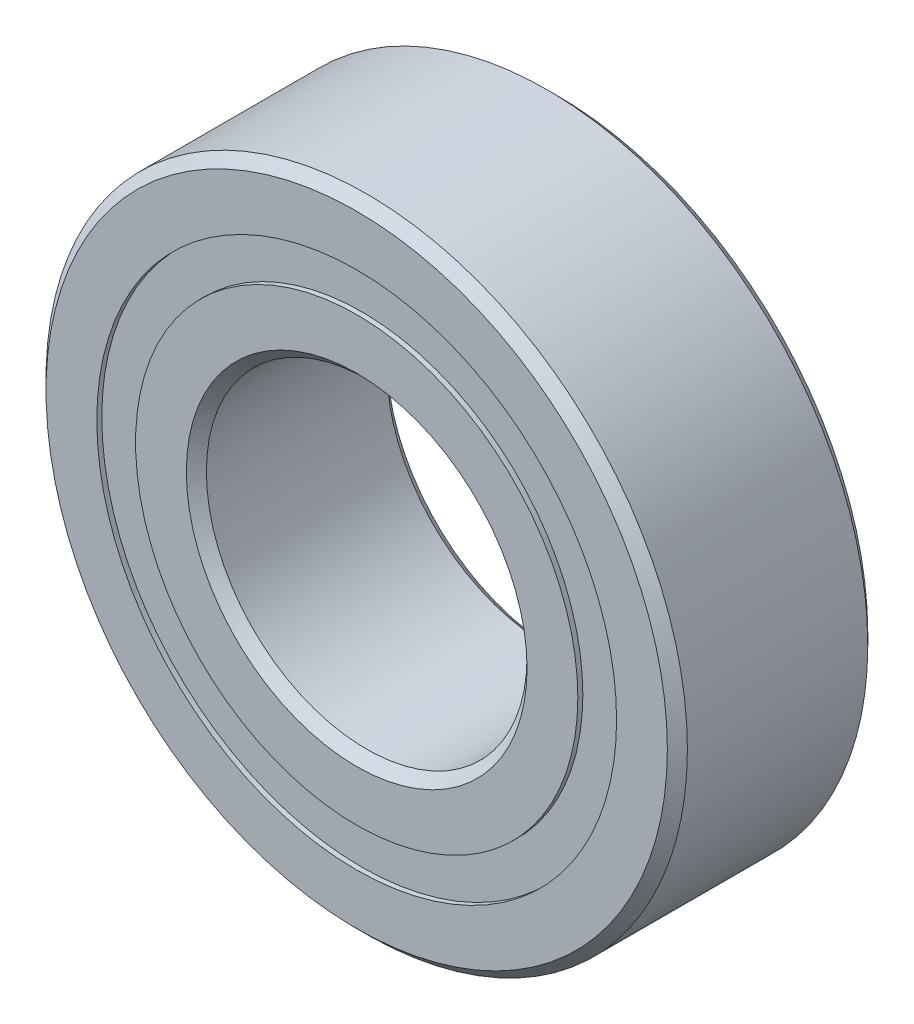
SolidWorks part; units mm, degrees
ref_plane "Front Plane" through (0, 0, 0) normal (0, 0, 1) x (1, 0, 0)
ref_plane "Top Plane" through (0, 0, 0) normal (0, 1, 0) x (1, 0, 0)
ref_plane "Right Plane" through (0, 0, 0) normal (1, 0, 0) x (0, 0, -1)
sketch "Sketch1" plane through (0, 0, 0) normal (1, 0, 0) x (0, 0, -1)
  line L0 (-2.5, 0) -> (2.5, 0) construction
  line L1 (0, 8) -> (0, -8) construction
  line L2 (2.25, 8) -> (-2.25, 8)
  line L3 (-2.25, 8) -> (-2.5, 7.75)
  line L4 (-2.5, 7.75) -> (-2.5, 6.4835)
  line L5 (-2.5, 6.4835) -> (-1.1111, 6.4835)
  line L6 (2.5, 6.4835) -> (1.1111, 6.4835)
  line L7 (2.5, 7.75) -> (2.5, 6.4835)
  line L8 (2.25, 8) -> (2.5, 7.75)
  line L9 (0, 8) -> (0, 6) construction
  line L10 (0, 6) -> (0, 4) construction
  arc A0 (-1.1111, 6.4835) -> (1.1111, 6.4835) centre (0, 6) cw
  point P14 (0, 4)
  dimension "Width" = 5
  dimension "OD" = 16
  dimension "D1" = 45
  dimension "D2" = 0.25
  dimension "Shaft Dia" = 8
  dimension "D3" = 2.2222
  dimension "D4" = 0.4835
revolve "Revolve1" add sketch "Sketch1" angle 360 about L0
sketch "Sketch3" plane through (0, 0, 0) normal (1, 0, 0) x (0, 0, -1)
  line L0 (-2.5, 5.5165) -> (-1.1111, 5.5165)
  line L1 (0, 8) -> (0, -8) construction
  line L2 (-2.5, 7.75) -> (-2.5, 6.4835) construction
  line L3 (-2.5, 5.5165) -> (-2.5, 4.25)
  line L4 (-2.25, 8) -> (-2.5, 7.75) construction
  line L5 (-2.5, 4.25) -> (-2.25, 4)
  line L6 (-2.25, 4) -> (2.25, 4)
  line L7 (2.25, 8) -> (2.25, -8) construction
  line L8 (2.25, 4) -> (2.5, 4.25)
  line L9 (2.5, -7.75) -> (2.5, 7.75) construction
  line L10 (2.5, 4.25) -> (2.5, 5.5165)
  line L11 (2.5, 5.5165) -> (1.1111, 5.5165)
  line L13 (2.25, 8) -> (2.5, 7.75) construction
  arc A0 (1.1111, 6.4835) -> (-1.1111, 6.4835) centre (0, 6) ccw construction
  arc A1 (1.1111, 5.5165) -> (-1.1111, 5.5165) centre (0, 6) cw
revolve "Revolve3" add sketch "Sketch3" angle 360 about L0
sketch "Sketch4" plane through (0, 0, 0) normal (1, 0, 0) x (0, 0, -1)
  line L0 (-1.2118, 6) -> (1.2118, 6)
  arc A2 (-1.2118, 6) -> (1.2118, 6) centre (0, 6) cw
  arc A3 (1.1111, 6.4835) -> (-1.1111, 6.4835) centre (0, 6) ccw construction
revolve "Revolve4" add sketch "Sketch4" angle 360 about L0
ref_axis "Axis1" through (0, 0, -2.5) along (0, 0, 1)
pattern_circular "CirPattern1" count 12 every 30 about axis through (0, 0, -2.5) along (0, 0, 1) of bodies 104
sketch "Sketch5" plane through (0, 0, 0) normal (1, 0, 0) x (0, 0, -1)
  line L0 (-2.5, 6.4835) -> (-1.1111, 6.4835) construction
  line L1 (-2.375, 6.4835) -> (-1.2118, 6.4835)
  line L2 (-2.375, 6.4835) -> (-2.375, 5.5165)
  line L3 (-2.375, 5.5165) -> (-1.2118, 5.5165)
  line L4 (-1.2118, 6.4835) -> (-1.2118, 5.5165)
  line L5 (-2.5, 5.5165) -> (-1.1111, 5.5165) construction
  line L6 (2.5, 6.4835) -> (1.1111, 6.4835) construction
  line L7 (2.375, 6.4835) -> (1.2118, 6.4835)
  line L8 (2.375, 6.4835) -> (2.375, 5.5165)
  line L9 (2.375, 5.5165) -> (1.2118, 5.5165)
  line L10 (1.2118, 6.4835) -> (1.2118, 5.5165)
  line L11 (2.5, 5.5165) -> (1.1111, 5.5165) construction
  line L12 (-2.25, 8) -> (-2.5, 7.75) construction
  point P18 (-2.375, 7.875)
revolve "Revolve5" add sketch "Sketch5" angle 360 about L0
sketch "Sketch6" plane through (0, 0, 0) normal (1, 0, 0) x (0, 0, -1)
  line L0 (2.5, 0) -> (-2.5, 0) construction
  line L1 (2.5, 6.4835) -> (1.4, 6.4835)
  line L2 (2.5, 6.4835) -> (2.5, 9.5)
  line L3 (2.5, 9.5) -> (1.4, 9.5)
  line L4 (1.4, 6.4835) -> (1.4, 9.5)
  dimension "Th" = 1.1
  dimension "Flange OD" = 19
revolve "Revolve6" [suppressed] add sketch "Sketch6" angle 360 about L0
equation "\"D2@Sketch1\" = \"Width@Sketch1\"*.05"
equation "\"D3@Sketch1\" = \"Width@Sketch1\"/2.25"
equation "\"D4@Sketch1\" = (((\"OD@Sketch1\"-\"Width@Sketch1\")/2)/3.25)/3.5"
equation "\"D2@CirPattern1\" = 360/\"Balls@CirPattern1\""
